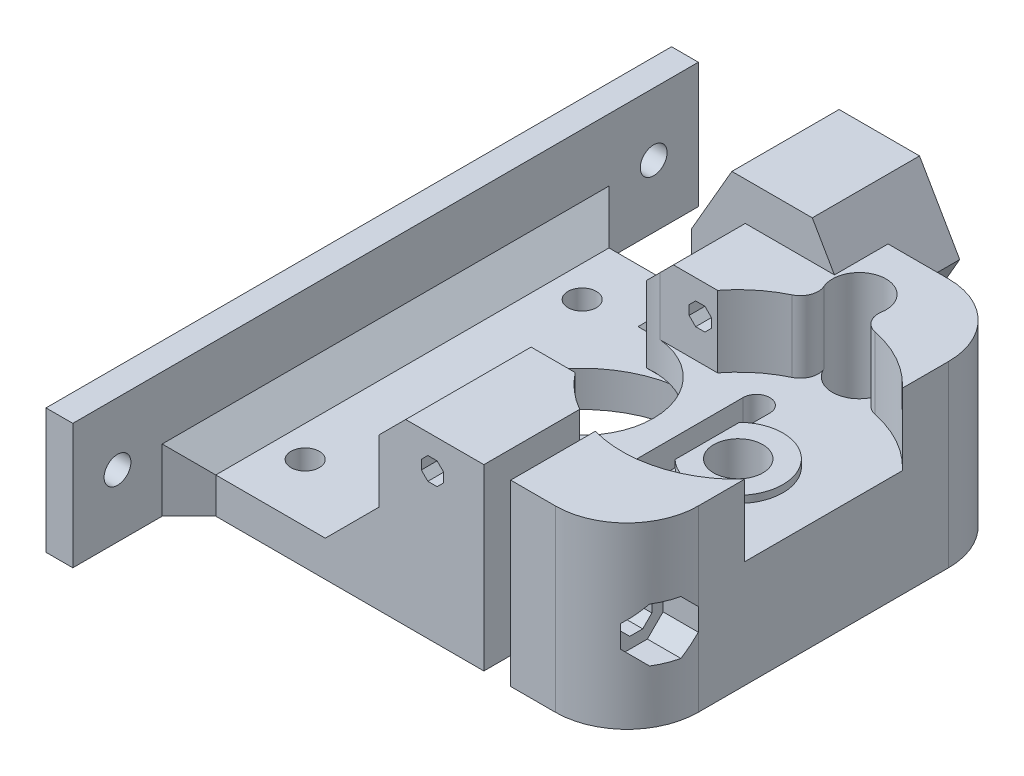
SolidWorks part; units mm, degrees
ref_plane "Front Plane" through (0, 0, 0) normal (0, 0, 1) x (1, 0, 0)
ref_plane "Top Plane" through (0, 0, 0) normal (0, 1, 0) x (1, 0, 0)
ref_plane "Right Plane" through (0, 0, 0) normal (1, 0, 0) x (0, 0, -1)
sketch "Sketch1" plane through (0, 0, 0) normal (0, 1, 0) x (1, 0, 0)
  line L0 (-44, 0) -> (0, 44) construction
  line L1 (0, 0) -> (-44, 0)
  line L2 (0, 0) -> (0, 44)
  line L3 (0, 44) -> (-44, 44)
  line L4 (-44, 0) -> (-44, 44)
  line L5 (-37.5, 37.5) -> (-6.5, 6.5) construction
  line L6 (-37.5, 6.5) -> (-6.5, 6.5) construction
  line L7 (-37.5, 6.5) -> (-37.5, 37.5) construction
  line L8 (-37.5, 37.5) -> (-6.5, 37.5) construction
  line L9 (-6.5, 6.5) -> (-6.5, 37.5) construction
  circle A0 centre (-22, 22) radius 12.5
  circle A1 centre (-37.5, 37.5) radius 1.5875
  circle A2 centre (-6.5, 37.5) radius 1.5875
  circle A3 centre (-37.5, 6.5) radius 1.5875
  circle A4 centre (-6.5, 6.5) radius 1.5875 construction
  point P10 (-22, 22)
  dimension "D1" = 25
  dimension "D2" = 3.175
  dimension "D3" = 44
  dimension "D4" = 31
extrude "Boss-Extrude1" add sketch "Sketch1" along normal blind 4
sketch "Sketch3" plane through (-44, 0, 0) normal (-1, 0, 0) x (0, 0, 1)
  line L0 (-57, 0) -> (13, 0)
  line L1 (-57, 0) -> (-57, 14)
  line L2 (-57, 14) -> (13, 14)
  line L3 (13, 0) -> (13, 14)
  line L4 (-22, 4) -> (-22, 14) construction
  line L5 (-44, 4) -> (0, 4) construction
  line L6 (-44, 0) -> (0, 0) construction
  dimension "D1" = 14
  dimension "D2" = 70
extrude "Boss-Extrude2" add sketch "Sketch3" along normal blind 3
sketch "Sketch4" plane through (0, 0, 0) normal (0, 0, 1) x (1, 0, 0)
  line L0 (-22, 0) -> (-22, 15.1967) construction
  line L1 (0, 4) -> (-22.75, 4)
  line L2 (0, 4) -> (0, 20)
  line L3 (0, 20) -> (-22.75, 20)
  line L4 (-22.75, 4) -> (-22.75, 20)
  line L5 (-44, 0) -> (0, 0) construction
  line L6 (-15.5, 17.0178) -> (-16.2322, 17.75)
  line L7 (-17.2678, 17.75) -> (-18, 17.0178)
  line L8 (-18, 17.0178) -> (-18, 15.9822)
  line L9 (-18, 15.9822) -> (-17.2678, 15.25)
  line L10 (-17.2678, 15.25) -> (-16.2322, 15.25)
  line L11 (-16.2322, 15.25) -> (-15.5, 15.9822)
  line L12 (-15.5, 15.9822) -> (-15.5, 17.0178)
  line L13 (-16.2322, 17.75) -> (-17.2678, 17.75)
  circle A1 centre (-16.75, 16.5) radius 1.25 construction
  dimension "D2" = 2.5
  dimension "D1" = 5.25
  dimension "D3" = 6
  dimension "D4" = 20
  dimension "D5" = 3.5
extrude "Boss-Extrude3" add sketch "Sketch4" against normal up to surface (44 mm away) up to face at (-22, 2, -44)
sketch "Sketch6" plane through (0, 0, 0) normal (1, 0, 0) x (0, 0, -1)
  line L4 (0, 0) -> (44, 0)
  line L5 (44, 0) -> (44, 20)
  line L6 (44, 20) -> (0, 20)
  line L7 (0, 20) -> (0, 0)
  line L8 (0, 0) -> (44, 0)
  line L9 (44, 0) -> (44, 20)
  line L10 (44, 20) -> (0, 20)
  line L11 (0, 20) -> (0, 0)
  dimension "D1" = 0
extrude "Boss-Extrude4" add sketch "Sketch6" along normal blind 5
sketch "Sketch7" plane through (0, 0, 0) normal (0, 1, 0) x (1, 0, 0)
  circle A0 centre (-22, 22) radius 8
  arc A1 (-22.75, 34.4775) -> (-22.75, 9.5225) centre (-22, 22) ccw construction
  dimension "D1" = 16
extrude "Cut-Extrude1" cut sketch "Sketch7" along normal through all both and the other way through all
sketch "Sketch8" plane through (-22.75, 0, 0) normal (-1, 0, 0) x (0, 0, 1)
  line L0 (-9.5225, 4) -> (0, 4) construction
  line L1 (-5.7249, 10.75) -> (-6.75, 9.7249)
  line L2 (-6.75, 9.7249) -> (-6.75, 8.2751)
  line L3 (-6.75, 8.2751) -> (-5.7249, 7.25)
  line L4 (-5.7249, 7.25) -> (-4.2751, 7.25)
  line L5 (-4.2751, 7.25) -> (-3.25, 8.2751)
  line L6 (-3.25, 8.2751) -> (-3.25, 9.7249)
  line L7 (-3.25, 9.7249) -> (-4.2751, 10.75)
  line L8 (-4.2751, 10.75) -> (-5.7249, 10.75)
  line L10 (0, 20) -> (0, 4) construction
  circle A0 centre (-5, 9) radius 1.75 construction
  point P1 (-5, 10.75)
  point P11 (-5, 7.25)
  dimension "D1" = 3.5
  dimension "D2" = 5
  dimension "D3" = 5
extrude "Cut-Extrude2" cut sketch "Sketch8" against normal through all
chamfer "Chamfer1" distance 4.5 angle 45 1 edges at (-14, 4, -22)
sketch "Sketch9" plane through (0, 20, 0) normal (0, 1, 0) x (1, 0, 0)
  line L0 (-4.5375, 0) -> (-4.5375, 44) construction
  line L1 (-22.75, 44) -> (5, 44) construction
  line L2 (5, 0) -> (-22.75, 0) construction
  circle A0 centre (-4.5375, 22) radius 13
  circle A1 centre (-22, 22) radius 4.4625 construction
  arc A2 (-22.75, 34.4775) -> (-22.75, 9.5225) centre (-22, 22) ccw construction
  dimension "D1" = 26
  dimension "D2" = 17.4625
extrude "Cut-Extrude3" cut sketch "Sketch9" against normal blind 8
sketch "Sketch20" plane through (0, 20, 0) normal (0, 1, 0) x (1, 0, 0)
  line L0 (5, 30.8338) -> (5, 13.1662) construction
  line L1 (-22.75, 29.9648) -> (5, 29.9648)
  line L2 (-22.75, 29.9648) -> (-22.75, 14.0352)
  line L3 (-22.75, 14.0352) -> (5, 14.0352)
  line L4 (5, 29.9648) -> (5, 14.0352)
  arc A0 (-22.75, 14.0352) -> (-16.2752, 16.4119) centre (-22, 22) ccw construction
extrude "Cut-Extrude11" cut sketch "Sketch20" against normal up to surface (8 mm away) up to face at (-5.499, 12, -22)
sketch "Sketch10" plane through (0, 12, 0) normal (0, 1, 0) x (1, 0, 0)
  circle A0 centre (-4.5375, 22) radius 5
  arc A1 (5, 30.8338) -> (-14.8119, 29.9648) centre (-4.5375, 22) ccw construction
  dimension "D1" = 10
extrude "Boss-Extrude5" add sketch "Sketch10" along normal blind 0.8
sketch "Sketch11" plane through (0, 12.8, 0) normal (0, 1, 0) x (1, 0, 0)
  circle A0 centre (-4.5375, 22) radius 2.75
  dimension "D1" = 5.5
extrude "Cut-Extrude4" cut sketch "Sketch11" against normal through all
sketch "Sketch12" plane through (-22.75, 0, 0) normal (-1, 0, 0) x (0, 0, 1)
  line L1 (-5, 12.3486) -> (-7.9, 10.6743)
  line L2 (-7.9, 10.6743) -> (-7.9, 7.3257)
  line L3 (-7.9, 7.3257) -> (-5, 5.6514)
  line L4 (-5, 5.6514) -> (-2.1, 7.3257)
  line L5 (-2.1, 7.3257) -> (-2.1, 10.6743)
  line L6 (-2.1, 10.6743) -> (-5, 12.3486)
  circle A0 centre (-5, 9) radius 2.9 construction
  circle A1 centre (-5, 9) radius 1.75 construction
  dimension "D1" = 5.8
extrude "Cut-Extrude5" cut sketch "Sketch12" against normal blind 3.8
sketch "Sketch13" plane through (0, 20, 0) normal (0, 1, 0) x (1, 0, 0)
  line L0 (-9.5, 29) -> (-9.5, 0) construction
  line L1 (-8, 29) -> (-8, 0)
  line L2 (-11, 29) -> (-11, 0)
  line L3 (5, 0) -> (-22.75, 0) construction
  arc A0 (-8, 29) -> (-11, 29) centre (-9.5, 29) ccw
  arc A1 (-11, 0) -> (-8, 0) centre (-9.5, 0) ccw
  arc A2 (-22.75, 34.4775) -> (-22.75, 9.5225) centre (-22, 22) ccw construction
  point P2 (-9.5, 14.5)
  dimension "D1" = 29
  dimension "D2" = 3
extrude "Cut-Extrude6" cut sketch "Sketch13" against normal through all
sketch "Sketch14" plane through (5, 0, 0) normal (1, 0, 0) x (0, 0, -1)
  line L0 (2, 7.7574) -> (3.7574, 6)
  line L1 (6.2426, 6) -> (8, 7.7574)
  line L2 (8, 7.7574) -> (8, 10.2426)
  line L3 (8, 10.2426) -> (6.2426, 12)
  line L4 (6.2426, 12) -> (3.7574, 12)
  line L5 (3.7574, 12) -> (2, 10.2426)
  line L6 (2, 10.2426) -> (2, 7.7574)
  line L7 (3.7574, 6) -> (6.2426, 6)
  circle A0 centre (5, 9) radius 3 construction
  circle A1 centre (5, 9) radius 1.75 construction
  dimension "D1" = 6
extrude "Cut-Extrude7" cut sketch "Sketch14" against normal offset from surface (3.95 mm away) 20 up to face at (-18.95, 9, -5)
sketch "Sketch15" plane through (0, 0, 0) normal (0, -1, 0) x (1, 0, 0)
  line L1 (-0.4725, -24.3469) -> (-0.4725, -19.6531)
  line L2 (-0.4725, -19.6531) -> (-4.5375, -17.3061)
  line L3 (-4.5375, -17.3061) -> (-8.6025, -19.6531)
  line L4 (-8.6025, -19.6531) -> (-8.6025, -24.3469)
  line L5 (-8.6025, -24.3469) -> (-4.5375, -26.6939)
  line L6 (-4.5375, -26.6939) -> (-0.4725, -24.3469)
  circle A0 centre (-4.5375, -22) radius 4.065 construction
  dimension "D1" = 8.13
extrude "Cut-Extrude8" cut sketch "Sketch15" against normal blind 4
sketch "Sketch16" plane through (0, 0, -44) normal (0, 0, -1) x (-1, 0, 0)
  line L0 (22.75, 4) -> (22.75, 20) construction
  line L2 (21.25, 24.2942) -> (12.25, 24.2942)
  line L3 (12.25, 24.2942) -> (7.75, 16.5)
  line L4 (7.75, 16.5) -> (12.25, 8.7058)
  line L5 (12.25, 8.7058) -> (21.25, 8.7058)
  line L6 (21.25, 8.7058) -> (25.75, 16.5)
  line L7 (25.75, 16.5) -> (21.25, 24.2942)
  circle A0 centre (16.75, 16.5) radius 7.7942 construction
  circle A1 centre (16.75, 16.5) radius 1.25 construction
  circle A2 centre (16.75, 16.5) radius 2
  dimension "D2" = 4
  dimension "D1" = 3
extrude "Boss-Extrude6" add sketch "Sketch16" along normal mid plane 12
sketch "Sketch17" plane through (0, 0, -50) normal (0, 0, -1) x (-1, 0, 0)
  line L0 (18.6968, 21.2) -> (14.8032, 21.2)
  line L1 (12.05, 18.4468) -> (12.05, 14.5532)
  line L2 (12.05, 14.5532) -> (14.8032, 11.8)
  line L3 (14.8032, 11.8) -> (18.6968, 11.8)
  line L4 (18.6968, 11.8) -> (21.45, 14.5532)
  line L5 (21.45, 14.5532) -> (21.45, 18.4468)
  line L6 (21.45, 18.4468) -> (18.6968, 21.2)
  line L7 (14.8032, 21.2) -> (12.05, 18.4468)
  circle A0 centre (16.75, 16.5) radius 4.7 construction
  circle A1 centre (16.75, 16.5) radius 1.25 construction
  dimension "D1" = 9.4
extrude "Cut-Extrude9" cut sketch "Sketch17" against normal blind 10
sketch "Sketch18" plane through (0, 4, 0) normal (0, 1, 0) x (1, 0, 0)
  line L0 (-25.75, 50) -> (-25.75, 38) construction
  line L1 (-22.75, 44) -> (-25.75, 44)
  line L2 (-22.75, 44) -> (-22.75, 38)
  line L3 (-22.75, 38) -> (-25.75, 38)
  line L4 (-25.75, 44) -> (-25.75, 38)
  line L5 (-9.7707, 38) -> (-22.75, 38) construction
  line L6 (-25.75, 38) -> (-21.25, 38) construction
extrude "Boss-Extrude7" add sketch "Sketch18" along normal up to surface (7.3038 mm away) up to face at (-23.25, 12.1699, -44)
sketch "Sketch19" plane through (0, 20, 0) normal (0, 1, 0) x (1, 0, 0)
  circle A0 centre (-6.5, 37.5) radius 3
  circle A1 centre (-6.5, 37.5) radius 1.5875 construction
  dimension "D1" = 6
extrude "Cut-Extrude10" cut sketch "Sketch19" against normal up to surface (16 mm away) up to face at (-37.5, 4, -35.9125)
chamfer "Chamfer2" distance 6 angle 45 1 edges at (-16.75, 8.7058, -44)
fillet "Fillet1" radius 8 2 edges at (5, 10, 0) (5, 10, -44)
chamfer "Chamfer3" distance 6 angle 45 2 edges at (-22.75, 4, -4.7613) (-25.75, 4, -41)
chamfer "Chamfer4" distance 3 angle 45 2 edges at (-22.75, 20, -7.0176) (-22.75, 20, -33.9824)
chamfer "Chamfer5" distance 3 angle 45 3 edges at (-44, 2, -44) (-44, 2, 0) (-44, 4, -22)
fillet "Fillet2" radius 2 2 edges at (-4.8473, 16, -34.9963) (-7.4766, 16, -34.6634)
sketch "Sketch21" plane through (-44, 0, 0) normal (1, 0, 0) x (0, 0, -1)
  line L0 (-3, 0) -> (-13, 0) construction
  line L2 (-13, 0) -> (-13, 14) construction
  line L3 (57, 14) -> (57, 0) construction
  circle A0 centre (-8, 7) radius 1.5
  circle A1 centre (52, 7) radius 1.5
  point P11 (57, 7)
  dimension "D1" = 3
  dimension "D2" = 7
  dimension "D3" = 5
  dimension "D4" = 5
extrude "Cut-Extrude12" cut sketch "Sketch21" against normal through all
